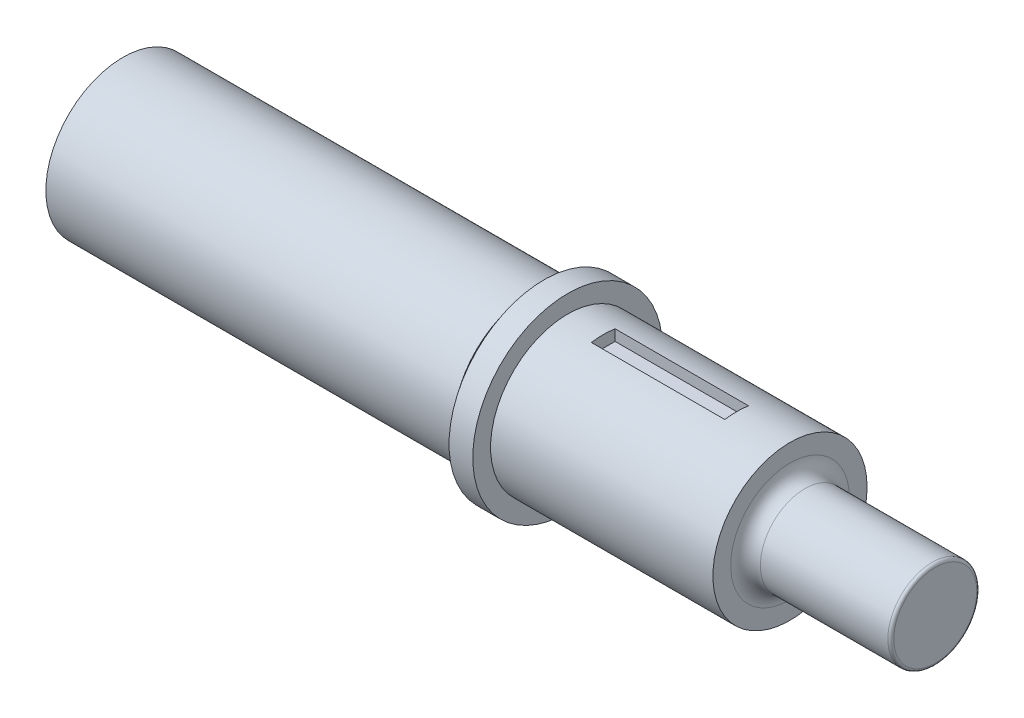
SolidWorks part; units mm, degrees
ref_plane "Front Plane" through (0, 0, 0) normal (0, 0, 1) x (1, 0, 0)
ref_plane "Top Plane" through (0, 0, 0) normal (0, 1, 0) x (1, 0, 0)
ref_plane "Right Plane" through (0, 0, 0) normal (1, 0, 0) x (0, 0, -1)
sketch "Sketch1" plane through (0, 0, 0) normal (1, 0, 0) x (0, 0, -1)
  circle A0 centre (0, 0) radius 26
extrude "Boss-Extrude1" add sketch "Sketch1" along normal blind 137.5
sketch "Sketch2" plane through (137.5, 0, 0) normal (1, 0, 0) x (0, 0, -1)
  circle A0 centre (0, 0) radius 22
extrude "Boss-Extrude2" add sketch "Sketch2" along normal blind 4.5
sketch "Sketch3" plane through (142, 0, 0) normal (1, 0, 0) x (0, 0, -1)
  circle A0 centre (0, 0) radius 32
extrude "Boss-Extrude3" add sketch "Sketch3" along normal blind 8
sketch "Sketch4" plane through (150, 0, 0) normal (1, 0, 0) x (0, 0, -1)
  circle A0 centre (0, 0) radius 26
extrude "Boss-Extrude4" add sketch "Sketch4" along normal blind 75
hole_wizard "Ø12.0 (12) Diameter Hole1" positions "3DSketch1" profile "Sketch5" hole size "Ø12.0" standard "ISO"
sketch3d "3DSketch1"
  line L0 (137.5, 0, 0) -> (0, 0, 0) construction
  point P0 (0, 0, 0)
  point P3 (0, 0, 0)
  point P6 (0, 0, 0)
  point P8 (0, 0, 0)
  point P12 (-153.5637, 12.3509, 0)
  point P14 (0, 0, 0)
  point P16 (0, 0, 0)
  point P18 (0, 0, 0)
  dimension "D1" = 0
sketch "Sketch5" plane through (0, 0, 0) normal (0, 1, 0) x (0, 0, 1)
  line L0 (0, 0) -> (0, 23.6052)
  line L1 (0, 23.6052) -> (6, 20)
  line L2 (6, 20) -> (6, 0)
  line L5 (6, 0) -> (0, 0)
  line L10 (0, 23.6052) -> (-6, 20) construction
  line L11 (0, -6.35) -> (0, 107.95) construction
  dimension "Hole Dia." = 12
  dimension "Hole Depth" = 20
  dimension "Drill Angle" = 118
cosmetic thread "Représentation de filetage1" parameters "D2"=13
cosmetic thread "Représentation de filetage2" parameters "D2"=13
sketch "Sketch6" plane through (225, 0, 0) normal (1, 0, 0) x (0, 0, -1)
  circle A0 centre (0, 0) radius 15
extrude "Boss-Extrude5" add sketch "Sketch6" along normal blind 49
cosmetic thread "Cosmetic Thread1" parameters "D1"=29, "D2"=26.158
fillet "Fillet2" radius 5 1 edges at (225, 0, -15)
sketch "Sketch7" plane through (0, 0, 0) normal (0, 1, 0) x (1, 0, 0)
  line L0 (225, 26) -> (150, 26) construction
  line L1 (162, -4) -> (207, -4)
  line L2 (162, -4) -> (162, 4)
  line L3 (162, 4) -> (207, 4)
  line L4 (207, -4) -> (207, 4)
  line L5 (150, -26) -> (225, -26) construction
  line L7 (150, -32) -> (150, 32) construction
  dimension "D1" = 30
  dimension "D2" = 30
  dimension "D4" = 12
  dimension "D3" = 45
extrude "Cut-Extrude1" cut sketch "Sketch7" against normal blind 4 from offset 26
sketch "Esquisse1" plane through (0, 0, 0) normal (-1, 0, 0) x (0, 0, 1)
  line L0 (0, -6) -> (0, -26) construction
  circle A0 centre (0, 0) radius 26 construction
  circle A4 centre (0, 0) radius 6 construction
  circle A5 centre (0, 0) radius 6 construction
  point P14 (0, -16)
  dimension "D1" = 20
  dimension "D2" = 0
hole_wizard "M8 Clearance Hole1" positions "Esquisse1" profile "Esquisse3" hole size "M8" standard "ANSI Metric"
sketch "Esquisse3" plane through (0, -16, 0) normal (0, 1, 0) x (0, 0, 1)
  line L0 (0, 0) -> (0, 15.5236)
  line L1 (0, 15.5236) -> (4.2, 13)
  line L2 (4.2, 13) -> (4.2, 0)
  line L5 (4.2, 0) -> (0, 0)
  line L10 (0, 15.5236) -> (-4.2, 13) construction
  line L11 (0, -6.35) -> (0, 107.95) construction
  dimension "Diamètre du perçage" = 8.4
  dimension "Profondeur du perçage" = 13
  dimension "Angle de pointe" = 118
cosmetic thread "Représentation de filetage3" parameters "D2"=10
cosmetic thread "Représentation de filetage4" parameters "D2"=10
sketch "Sketch8" plane through (0, 0, 0) normal (0, 0, 1) x (1, 0, 0)
  line L0 (150, 0) -> (244, 0) construction
  line L1 (150, -32) -> (150, 32) construction
  line L2 (244, 0) -> (274, 0) construction
  line L3 (274, -15) -> (274, 15) construction
  dimension "D1" = 94
  dimension "D2" = 124
sketch "Sketch9" plane through (0, 0, 0) normal (0, 0, 1) x (1, 0, 0)
  line L0 (0, 0) -> (150, 0) construction
  line L1 (0, 26) -> (0, -26) construction
  line L2 (142, 32) -> (142, -32) construction
  point P5 (142, 0)
fillet "Fillet3" radius 1 1 edges at (274, 0, -15)
equation "\"D2@Sketch7\"=\"D1@Sketch7\""
